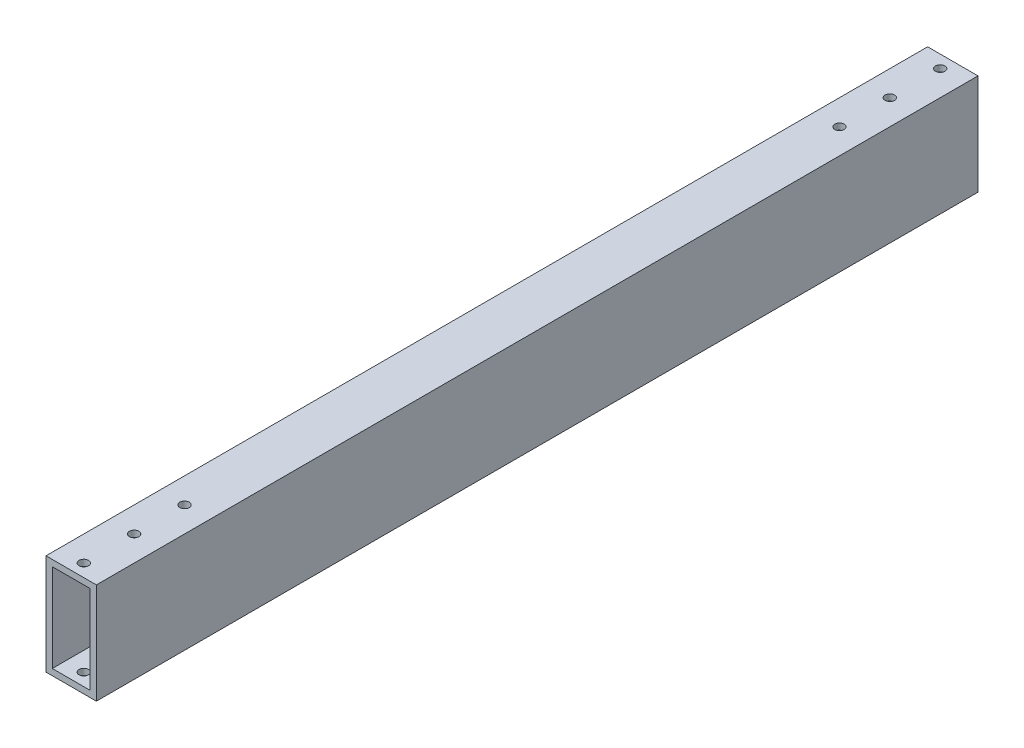
SolidWorks part; units mm, degrees
material "6063-T1"
ref_plane "Front Plane" through (0, 0, 0) normal (0, 0, 1) x (1, 0, 0)
ref_plane "Top Plane" through (0, 0, 0) normal (0, 1, 0) x (1, 0, 0)
ref_plane "Right Plane" through (0, 0, 0) normal (1, 0, 0) x (0, 0, -1)
sketch "Sketch1" plane through (0, 0, 0) normal (0, 0, 1) x (1, 0, 0)
  line L1 (-12.7, 25.4) -> (12.7, 25.4)
  line L2 (-12.7, 25.4) -> (-12.7, -25.4)
  line L3 (-12.7, -25.4) -> (12.7, -25.4)
  line L4 (12.7, 25.4) -> (12.7, -25.4)
  line L5 (-12.7, 25.4) -> (12.7, -25.4) construction
  line L6 (-12.7, -25.4) -> (12.7, 25.4) construction
  point P0 (0, 0)
  dimension "D1" = 25.4
  dimension "D2" = 50.8
extrude "Boss-Extrude1" add sketch "Sketch1" along normal blind 444.5
shell "Shell1" thickness 3.175 removed face at (0, 0, 0) removed face at (0, 0, 444.5)
sketch "Sketch2" plane through (0, 25.4, 0) normal (0, 1, 0) x (1, 0, 0)
  line L0 (12.7, 0) -> (-12.7, 0) construction
  line L1 (12.7, -222.25) -> (-14.2289, -222.25) construction
  line L2 (12.7, -444.5) -> (12.7, 0) construction
  circle A0 centre (0, -6.35) radius 2.3812
  circle A3 centre (0, -31.75) radius 2.3812
  circle A4 centre (0, -57.15) radius 2.3812
  circle A5 centre (0, -387.35) radius 2.3812
  circle A6 centre (0, -412.75) radius 2.3812
  circle A7 centre (0, -438.15) radius 2.3813
  dimension "D1" = 4.7625
  dimension "D2" = 6.35
  dimension "D3" = 3
extrude "Cut-Extrude1" cut sketch "Sketch2" against normal through all
